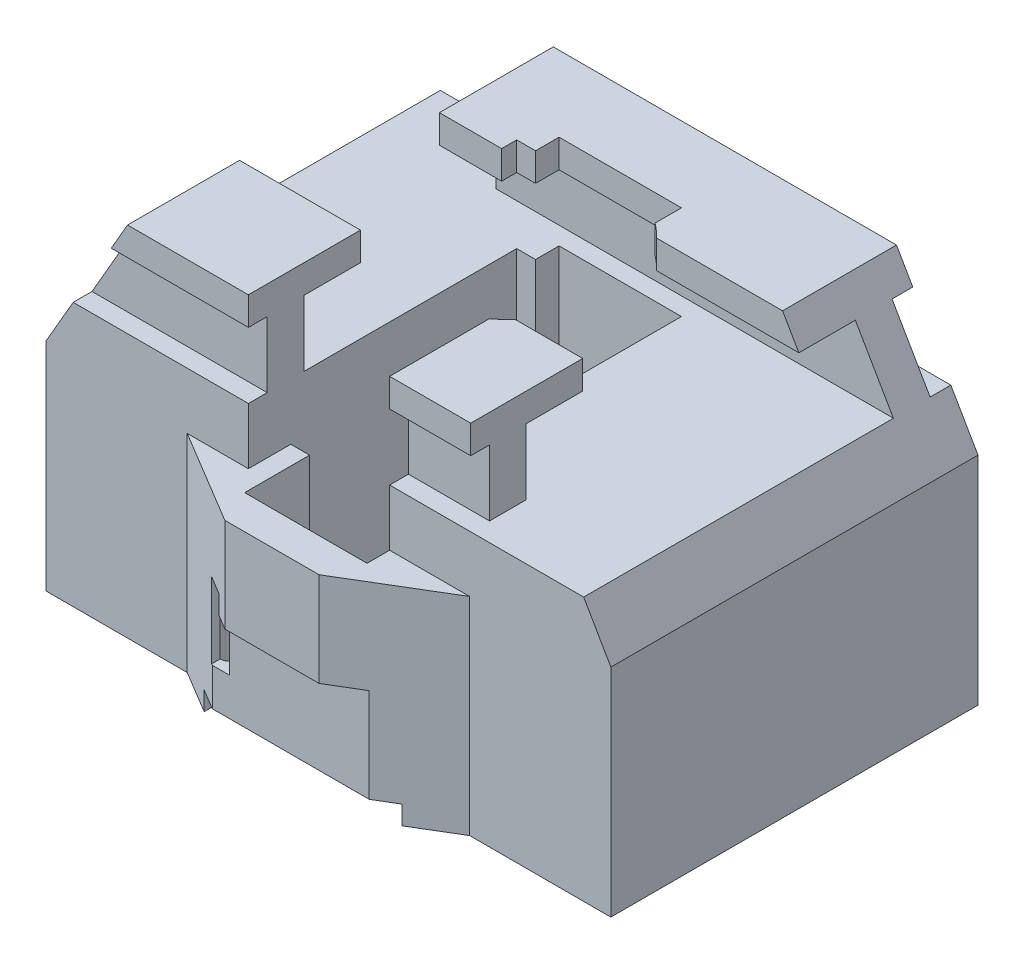
SolidWorks part; units mm, degrees
ref_plane "Front Plane" through (0, 0, 0) normal (0, 0, 1) x (1, 0, 0)
ref_plane "Top Plane" through (0, 0, 0) normal (0, 1, 0) x (1, 0, 0)
ref_plane "Right Plane" through (0, 0, 0) normal (1, 0, 0) x (0, 0, -1)
sketch "Sketch1" plane through (0, 0, 0) normal (0, 1, 0) x (1, 0, 0)
  line L1 (-60, 45) -> (0, 45)
  line L2 (-60, 45) -> (-60, 0)
  line L3 (-60, 0) -> (0, 0)
  line L4 (0, 45) -> (0, 0)
  dimension "D1" = 60
  dimension "D2" = 45
extrude "Boss-Extrude1" add sketch "Sketch1" along normal blind 30
sketch "Sketch2" plane through (0, 0, 0) normal (0, -1, 0) x (-1, 0, 0)
  line L0 (60, 45) -> (60, 0) construction
  line L1 (50.75, 13) -> (44.25, 13)
  line L2 (50.75, 13) -> (50.75, 29)
  line L3 (50.75, 29) -> (44.25, 29)
  line L4 (44.25, 13) -> (44.25, 29)
  line L5 (16.25, 13) -> (9.75, 13)
  line L6 (16.25, 13) -> (16.25, 29)
  line L7 (16.25, 29) -> (9.75, 29)
  line L8 (9.75, 13) -> (9.75, 29)
  line L10 (0, 0) -> (0, 45) construction
  line L12 (0, 45) -> (60, 45) construction
  dimension "D1" = 16
  dimension "D2" = 6.5
  dimension "D3" = 9.25
  dimension "D4" = 6.5
  dimension "D5" = 16
  dimension "D6" = 9.75
  dimension "D7" = 16
extrude "Cut-Extrude1" cut sketch "Sketch2" against normal blind 20
chamfer "Chamfer1" distance 5 angle 5 4 edges at (-16.25, 20, -21) (-9.75, 20, -21) (-50.75, 20, -21) (-44.25, 20, -21) first distance on face at (-16.25, 10, -21) first distance on face at (-9.75, 10, -21) first distance on face at (-50.75, 10, -21) first distance on face at (-44.25, 10, -21)
chamfer "Chamfer2" distance 5 angle 50 4 edges at (-47.5, 20, -29) (-13, 20, -29) (-13, 20, -13) (-47.5, 20, -13) first distance on face at (-47.5, 11.6667, -29) first distance on face at (-13, 11.6667, -29) first distance on face at (-13, 11.6667, -13) first distance on face at (-47.5, 11.6667, -13)
sketch "Sketch4" plane through (0, 0, -45) normal (0, 0, -1) x (-1, 0, 0)
  line L0 (11.5, 0) -> (28.3, 0)
  line L1 (0, 0) -> (60, 0) construction
  arc A0 (28.3, 0) -> (42.6119, 6.1301) centre (38.1836, -3.3031) cw
  arc A1 (42.6119, 6.1301) -> (46.2306, 12.0745) centre (44.0992, 9.2984) ccw
  arc A2 (46.2306, 12.0745) -> (11.5, 0) centre (32.8331, -5.3756) ccw
  dimension "D3" = 3.5
  dimension "D4" = 10.4209
  dimension "D7" = 22
  dimension "D1" = 16.8
  dimension "D2" = 11.5
  dimension "D5" = 3.3031
  dimension "D6" = 9.2984
extrude "Cut-Extrude2" cut sketch "Sketch4" against normal blind 10
chamfer "Chamfer3" distance 3 distance2 1.5 8 edges at (-13, 0, -13) (-9.75, 0, -21) (-13, 0, -29) (-16.25, 0, -21) (-47.5, 0, -29) (-44.25, 0, -21) (-47.5, 0, -13) (-50.75, 0, -21) first distance on face at (-47.5, 0, -21)
sketch "Sketch5" plane through (-60, 0, 0) normal (-1, 0, 0) x (0, 0, 1)
  line L0 (0, 30) -> (0, 0) construction
  line L1 (-45, 30) -> (0, 30)
  line L2 (-45, 30) -> (-45, 22)
  line L4 (0, 30) -> (0, 0)
  line L5 (-45, 22) -> (-6, 22)
  line L6 (-6, 22) -> (-6, 0)
  line L7 (-45, 0) -> (0, 0) construction
  line L8 (-6, 0) -> (0, 0)
  dimension "D1" = 8
extrude "Cut-Extrude3" cut sketch "Sketch5" against normal up to next
sketch "Sketch6" plane through (0, 0, 0) normal (0, -1, 0) x (-1, 0, 0)
  line L1 (44.25, 37) -> (16.25, 37)
  line L2 (44.25, 37) -> (44.25, 6)
  line L3 (44.25, 6) -> (16.25, 6)
  line L4 (16.25, 37) -> (16.25, 6)
  line L5 (44.25, 29) -> (44.25, 13) construction
  line L6 (0, 6) -> (60, 6) construction
  line L7 (16.25, 13) -> (16.25, 29) construction
  dimension "D1" = 31
extrude "Cut-Extrude4" cut sketch "Sketch6" against normal blind 1
sketch "Sketch12" plane through (0, 0, 0) normal (0, -1, 0) x (1, 0, 0)
  line L0 (-45, -6) -> (-35, 0)
  line L1 (-44.25, -6) -> (-60, -6) construction
  line L2 (-35, 0) -> (-25, 0)
  line L3 (-25, 0) -> (-15, -6)
  line L4 (-15, -6) -> (-45, -6)
  point P7 (-36.3267, 0)
  dimension "D1" = 30
  dimension "D2" = 15
  dimension "D3" = 6
  dimension "D4" = 10
  dimension "D5" = 10
extrude "Boss-Extrude2" add sketch "Sketch12" against normal up to surface (22 mm away) up to face at (-30, 22, -25.5)
sketch "Sketch7" plane through (0, 22, 0) normal (0, 1, 0) x (1, 0, 0)
  line L1 (-23.5, 8.6) -> (-36.5, 8.6)
  line L2 (-23.5, 8.6) -> (-23.5, 32)
  line L3 (-23.5, 32) -> (-36.5, 32)
  line L4 (-36.5, 8.6) -> (-36.5, 32)
  line L6 (0, 45) -> (-60, 45) construction
  line L9 (0, 6) -> (0, 45) construction
  circle A0 centre (-30, 25.5) radius 1.6355 construction
  dimension "D5" = 3.2709
  dimension "D1" = 13
  dimension "D2" = 23.5
  dimension "D3" = 19.5
  dimension "D4" = 30
  dimension "D6" = 16.9
  dimension "D7" = 6.5
extrude "Cut-Extrude5" cut sketch "Sketch7" against normal up to next
sketch "Sketch8" plane through (0, 1, 0) normal (0, -1, 0) x (1, 0, 0)
  line L1 (-36.5, -8.6) -> (-23.5, -8.6)
  line L2 (-36.5, -8.6) -> (-36.5, -3.6)
  line L3 (-36.5, -3.6) -> (-23.5, -3.6)
  line L4 (-23.5, -8.6) -> (-23.5, -3.6)
  line L5 (-36.5, -8.6) -> (-36.5, -32) construction
  line L6 (-23.5, -32) -> (-36.5, -32)
  line L7 (-23.5, -32) -> (-23.5, -37)
  line L8 (-23.5, -37) -> (-36.5, -37)
  line L9 (-36.5, -32) -> (-36.5, -37)
  line L10 (-23.5, -32) -> (-23.5, -8.6) construction
  point P5 (0, 0)
  point P6 (0, 0)
  point P16 (0, 0)
  dimension "D1" = 5
  dimension "D2" = 5
extrude "Cut-Extrude6" cut sketch "Sketch8" against normal up to next from offset 15.6 offset against normal yes
sketch "Sketch10" plane through (0, 22, 0) normal (0, 1, 0) x (1, 0, 0)
  line L0 (-27.5, 32) -> (-27.5, 34.5)
  line L1 (-23.5, 32) -> (-36.5, 32) construction
  line L2 (-27.5, 34.5) -> (-38.5, 34.5)
  line L3 (-38.5, 34.5) -> (-38.5, 10.5)
  line L4 (-38.5, 10.5) -> (-36.5, 10.5)
  line L5 (-36.5, 37) -> (-36.5, 3.6) construction
  line L6 (-36.5, 10.5) -> (-36.5, 32)
  line L7 (-36.5, 32) -> (-27.5, 32)
  dimension "D1" = 2.5
  dimension "D2" = 9
  dimension "D3" = 11
  dimension "D4" = 24
extrude "Cut-Extrude7" cut sketch "Sketch10" against normal up to next
sketch "Sketch13" plane through (0, 22, 0) normal (0, 1, 0) x (1, 0, 0)
  line L0 (-60, 45) -> (0, 45)
  line L1 (0, 45) -> (0, 6)
  line L2 (0, 6) -> (-15, 6)
  line L3 (-15, 6) -> (-23.5, 6)
  line L4 (-23.5, 3.6) -> (-23.5, 37) construction
  line L5 (-23.5, 6) -> (-23.5, 37)
  line L6 (-23.5, 37) -> (-36.5, 37)
  line L7 (-36.5, 37) -> (-36.5, 34.5)
  line L8 (-36.5, 34.5) -> (-38.5, 34.5)
  line L9 (-38.5, 34.5) -> (-38.5, 6)
  line L10 (-38.5, 6) -> (-60, 6)
  line L11 (-60, 6) -> (-60, 45)
extrude "Boss-Extrude3" add sketch "Sketch13" along normal blind 16
chamfer "Chamfer6" distance 15 angle 30 2 edges at (-60, 38, -25.5) (0, 38, -25.5) first distance on face at (-60, 19, -25.5) first distance on face at (0, 19, -25.5)
sketch "Sketch14" plane through (0, 38, 0) normal (0, 1, 0) x (1, 0, 0)
  line L0 (-38.5, 6) -> (-38.5, 34.5) construction
  line L1 (-36.5, 37) -> (-23.5, 37) construction
  circle A0 centre (-30.1, 25.4) radius 11
  point P3 (0, 0)
  dimension "D1" = 22
  dimension "D2" = 8.4
  dimension "D3" = 11.6
extrude "Cut-Extrude8" cut sketch "Sketch14" against normal blind 10
sketch "Sketch15" plane through (0, 38, 0) normal (0, 1, 0) x (1, 0, 0)
  line L1 (-65.1, 32.9) -> (4.9, 32.9)
  line L2 (-65.1, 32.9) -> (-65.1, 17.9)
  line L3 (-65.1, 17.9) -> (4.9, 17.9)
  line L4 (4.9, 32.9) -> (4.9, 17.9)
  arc A0 (-23.5, 16.6) -> (-23.5, 34.2) centre (-30.1, 25.4) ccw construction
  dimension "D1" = 15
  dimension "D2" = 7.5
  dimension "D3" = 70
  dimension "D4" = 35
extrude "Cut-Extrude9" cut sketch "Sketch15" against normal up to surface (10 mm away) up to face at (-39.8, 28, -25.4)
sketch "Sketch16" plane through (-38.5, 0, 0) normal (1, 0, 0) x (0, 0, -1)
  line L0 (6, 38) -> (6, 22) construction
  line L1 (17.9, 28) -> (11.9, 28)
  line L2 (17.9, 28) -> (17.9, 35)
  line L3 (17.9, 35) -> (11.9, 35)
  line L4 (11.9, 28) -> (11.9, 35)
  line L5 (6, 28) -> (8, 28)
  line L6 (6, 28) -> (6, 35)
  line L7 (6, 35) -> (8, 35)
  line L8 (8, 28) -> (8, 35)
  dimension "D1" = 2
  dimension "D2" = 6
  dimension "D3" = 7
  dimension "D4" = 7
extrude "Cut-Extrude10" cut sketch "Sketch16" against normal through all both and the other way through all
sketch "Sketch17" plane through (-38.5, 0, 0) normal (1, 0, 0) x (0, 0, -1)
  line L0 (45, 23) -> (45, 38) construction
  line L1 (32.9, 28) -> (38.9, 28)
  line L2 (32.9, 28) -> (32.9, 35)
  line L3 (32.9, 35) -> (38.9, 35)
  line L4 (38.9, 28) -> (38.9, 35)
  line L5 (45, 28) -> (42.8, 28)
  line L6 (45, 28) -> (45, 35)
  line L7 (45, 35) -> (42.8, 35)
  line L8 (42.8, 28) -> (42.8, 35)
  dimension "D1" = 7
  dimension "D2" = 6
  dimension "D3" = 3.9
extrude "Cut-Extrude11" cut sketch "Sketch17" against normal through all both and the other way through all
sketch "Sketch18" plane through (0, 0, 0) normal (0, -1, 0) x (1, 0, 0)
  line L1 (-40.5, 2) -> (-19.5, 2)
  line L2 (-40.5, 2) -> (-40.5, -6)
  line L3 (-40.5, -6) -> (-19.5, -6)
  line L4 (-19.5, 2) -> (-19.5, -6)
  dimension "D1" = 21
  dimension "D2" = 4.5
  dimension "D3" = 8
  dimension "D4" = 0
extrude "Cut-Extrude12" cut sketch "Sketch18" against normal blind 2
sketch "Sketch19" plane through (0, 2, 0) normal (0, -1, 0) x (1, 0, 0)
  line L0 (-40.5, -3.3) -> (-40.5, -6) construction
  line L1 (-19.5, -6) -> (-40.5, -6) construction
  line L2 (-35, 0) -> (-25, 0) construction
  line L3 (-39.1705, 3.1892) -> (-20.8295, 3.1892)
  line L4 (-39.1705, 3.1892) -> (-39.1705, -2)
  line L5 (-39.1705, -2) -> (-20.8295, -2)
  line L6 (-20.8295, 3.1892) -> (-20.8295, -2)
  circle A0 centre (-38.5, -4) radius 1
  circle A1 centre (-22.5, -4) radius 1
  dimension "D1" = 2
  dimension "D2" = 16
  dimension "D3" = 2
  dimension "D4" = 2
  dimension "D5" = 2
extrude "Cut-Extrude13" cut sketch "Sketch19" against normal blind 10
sketch "Sketch20" plane through (0, 0, -10.5) normal (0, 0, -1) x (-1, 0, 0)
  line L0 (38.5, 1) -> (38.5, 22) construction
  line L1 (38.5, 14) -> (36.5, 14)
  line L2 (38.5, 14) -> (38.5, 6)
  line L3 (38.5, 6) -> (36.5, 6)
  line L4 (36.5, 14) -> (36.5, 6)
  line L5 (36.5, 1) -> (36.5, 22) construction
  line L6 (36.5, 1) -> (38.5, 1) construction
  point P10 (37.5, 1)
  dimension "D1" = 5
  dimension "D2" = 8
extrude "Cut-Extrude14" cut sketch "Sketch20" against normal up to next
sketch "Sketch21" plane through (0, 38, 0) normal (0, 1, 0) x (1, 0, 0)
  line L0 (-2.8868, 6) -> (-2.8868, 8) construction
  line L1 (-61.9141, 51.6985) -> (-45.1132, 51.6985)
  line L2 (-61.9141, 51.6985) -> (-61.9141, 28.5299)
  line L3 (-61.9141, 28.5299) -> (-45.1132, 28.5299)
  line L4 (-45.1132, 51.6985) -> (-45.1132, 28.5299)
  line L5 (10.427, -5.5418) -> (-14.8868, -5.5418)
  line L6 (10.427, -5.5418) -> (10.427, 21.7171)
  line L7 (10.427, 21.7171) -> (-14.8868, 21.7171)
  line L8 (-14.8868, -5.5418) -> (-14.8868, 21.7171)
  dimension "D1" = 12
  dimension "D2" = 12
extrude "Cut-Extrude15" cut sketch "Sketch21" against normal up to surface (10 mm away) up to face at (-30, 28, -43.9)
equation "\"D2@Sketch12\"=(60-\"D1@Sketch12\")/2"
equation "\"D5@Sketch12\"=(\"D1@Sketch12\"-\"D4@Sketch12\")/2"
equation "\"D2@Sketch15\"=\"D1@Sketch15\"/2"
equation "\"D4@Sketch16\"=\"D3@Sketch16\""
equation "\"D2@Sketch18\"=(30-\"D1@Sketch18\")/2"
equation "\"D3@Sketch19\"=(20-\"D2@Sketch19\")/2"
equation "\"D4@Sketch19\"=\"D3@Sketch19\""
